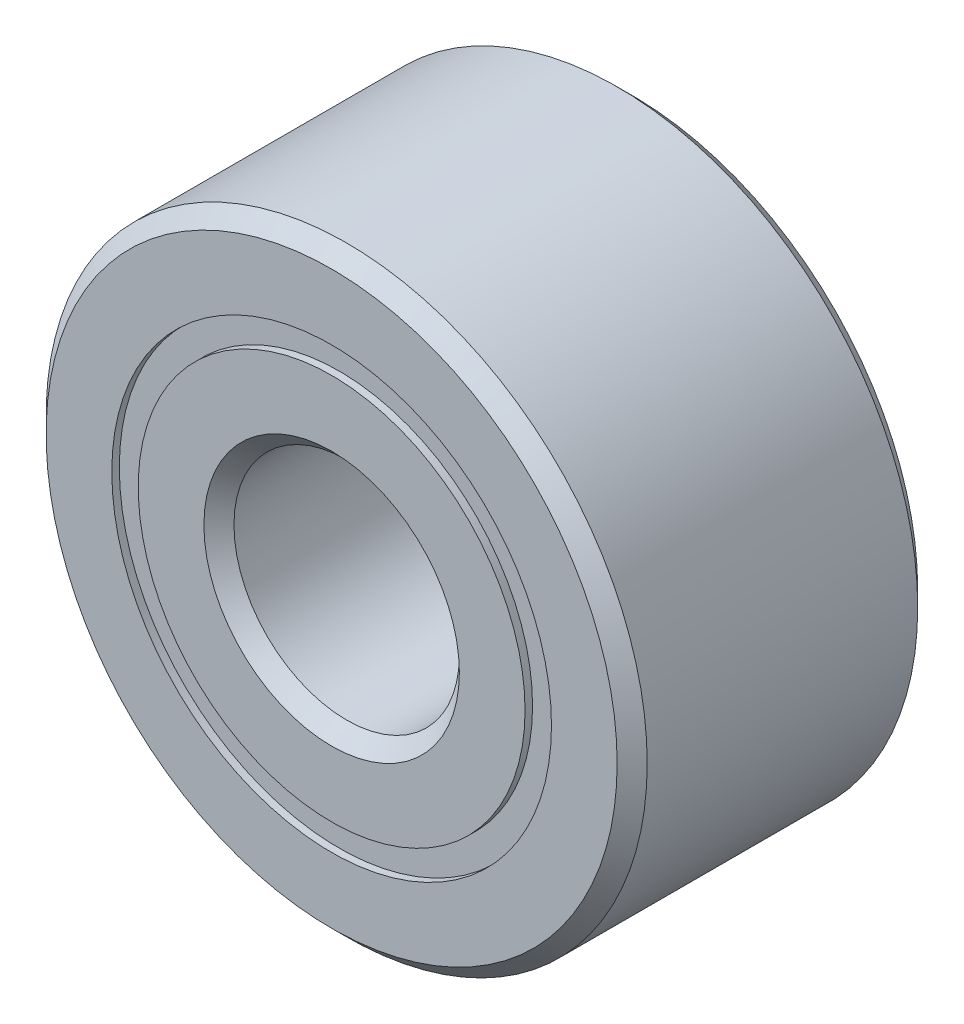
SolidWorks part; units mm, degrees
ref_plane "Front Plane" through (0, 0, 0) normal (0, 0, 1) x (1, 0, 0)
ref_plane "Top Plane" through (0, 0, 0) normal (0, 1, 0) x (1, 0, 0)
ref_plane "Right Plane" through (0, 0, 0) normal (1, 0, 0) x (0, 0, -1)
sketch "Sketch1" plane through (0, 0, 0) normal (1, 0, 0) x (0, 0, -1)
  line L0 (-2, 0) -> (2, 0) construction
  line L1 (0, 4) -> (0, -4) construction
  line L2 (1.8, 4) -> (-1.8, 4)
  line L3 (-1.8, 4) -> (-2, 3.8)
  line L4 (-2, 3.8) -> (-2, 2.9258)
  line L5 (-2, 2.9258) -> (-0.8889, 2.9258)
  line L6 (2, 2.9258) -> (0.8889, 2.9258)
  line L7 (2, 3.8) -> (2, 2.9258)
  line L8 (1.8, 4) -> (2, 3.8)
  line L9 (0, 4) -> (0, 2.75) construction
  line L10 (0, 2.75) -> (0, 1.5) construction
  arc A0 (-0.8889, 2.9258) -> (0.8889, 2.9258) centre (0, 2.75) cw
  point P14 (0, 1.5)
  dimension "Width" = 4
  dimension "OD" = 8
  dimension "D1" = 45
  dimension "D2" = 0.2
  dimension "Shaft Dia" = 3
  dimension "D3" = 1.7778
  dimension "D4" = 0.1758
revolve "Revolve1" add sketch "Sketch1" angle 360 about L0
sketch "Sketch3" plane through (0, 0, 0) normal (1, 0, 0) x (0, 0, -1)
  line L0 (-2, 2.5742) -> (-0.8889, 2.5742)
  line L1 (0, 4) -> (0, -4) construction
  line L2 (-2, 3.8) -> (-2, 2.9258) construction
  line L3 (-2, 2.5742) -> (-2, 1.7)
  line L4 (-1.8, 4) -> (-2, 3.8) construction
  line L5 (-2, 1.7) -> (-1.8, 1.5)
  line L6 (-1.8, 1.5) -> (1.8, 1.5)
  line L7 (1.8, 4) -> (1.8, -4) construction
  line L8 (1.8, 1.5) -> (2, 1.7)
  line L9 (2, -3.8) -> (2, 3.8) construction
  line L10 (2, 1.7) -> (2, 2.5742)
  line L11 (2, 2.5742) -> (0.8889, 2.5742)
  line L13 (1.8, 4) -> (2, 3.8) construction
  arc A0 (0.8889, 2.9258) -> (-0.8889, 2.9258) centre (0, 2.75) ccw construction
  arc A1 (0.8889, 2.5742) -> (-0.8889, 2.5742) centre (0, 2.75) cw
revolve "Revolve3" add sketch "Sketch3" angle 360 about L0
sketch "Sketch4" plane through (0, 0, 0) normal (1, 0, 0) x (0, 0, -1)
  line L0 (-0.9061, 2.75) -> (0.9061, 2.75)
  arc A2 (-0.9061, 2.75) -> (0.9061, 2.75) centre (0, 2.75) cw
  arc A3 (0.8889, 2.9258) -> (-0.8889, 2.9258) centre (0, 2.75) ccw construction
revolve "Revolve4" add sketch "Sketch4" angle 360 about L0
ref_axis "Axis1" through (0, 0, -2) along (0, 0, 1)
pattern_circular "CirPattern1" count 12 every 30 about axis through (0, 0, -2) along (0, 0, 1) of bodies 104
sketch "Sketch5" plane through (0, 0, 0) normal (1, 0, 0) x (0, 0, -1)
  line L0 (-2, 2.9258) -> (-0.8889, 2.9258) construction
  line L1 (-1.9, 2.9258) -> (-0.9061, 2.9258)
  line L2 (-1.9, 2.9258) -> (-1.9, 2.5742)
  line L3 (-1.9, 2.5742) -> (-0.9061, 2.5742)
  line L4 (-0.9061, 2.9258) -> (-0.9061, 2.5742)
  line L5 (-2, 2.5742) -> (-0.8889, 2.5742) construction
  line L6 (2, 2.9258) -> (0.8889, 2.9258) construction
  line L7 (1.9, 2.9258) -> (0.9061, 2.9258)
  line L8 (1.9, 2.9258) -> (1.9, 2.5742)
  line L9 (1.9, 2.5742) -> (0.9061, 2.5742)
  line L10 (0.9061, 2.9258) -> (0.9061, 2.5742)
  line L11 (2, 2.5742) -> (0.8889, 2.5742) construction
  line L12 (-1.8, 4) -> (-2, 3.8) construction
  point P18 (-1.9, 3.9)
revolve "Revolve5" add sketch "Sketch5" angle 360 about L0
sketch "Sketch6" plane through (0, 0, 0) normal (1, 0, 0) x (0, 0, -1)
  line L0 (2, 0) -> (-2, 0) construction
  line L1 (2, 2.9258) -> (1.2126, 2.9258)
  line L2 (2, 2.9258) -> (2, 6.9469)
  line L3 (2, 6.9469) -> (1.2126, 6.9469)
  line L4 (1.2126, 2.9258) -> (1.2126, 6.9469)
  dimension "Th" = 0.7874
  dimension "Flange OD" = 13.8938
equation "\"D2@Sketch1\" = \"Width@Sketch1\"*.05"
equation "\"D3@Sketch1\" = \"Width@Sketch1\"/2.25"
equation "\"D4@Sketch1\" = (((\"OD@Sketch1\"-\"Width@Sketch1\")/2)/3.25)/3.5"
equation "\"D2@CirPattern1\" = 360/\"Balls@CirPattern1\""
